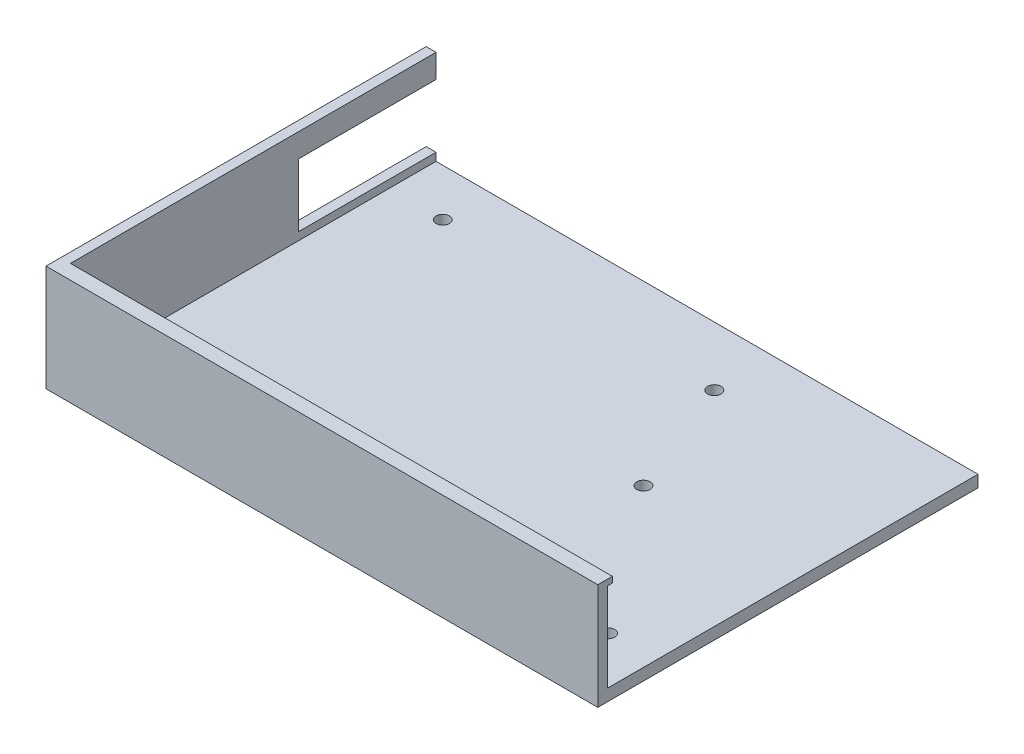
SolidWorks part; units mm, degrees
ref_plane "Front Plane" through (0, 0, 0) normal (0, 0, 1) x (1, 0, 0)
ref_plane "Top Plane" through (0, 0, 0) normal (0, 1, 0) x (1, 0, 0)
ref_plane "Right Plane" through (0, 0, 0) normal (1, 0, 0) x (0, 0, -1)
sketch "Sketch1" plane through (0, 0, 0) normal (0, 1, 0) x (1, 0, 0)
  line L1 (-140.2, -96.6) -> (140.2, -96.6)
  line L2 (-140.2, -96.6) -> (-140.2, 96.6)
  line L3 (-140.2, 96.6) -> (140.2, 96.6)
  line L4 (140.2, -96.6) -> (140.2, 96.6)
  line L5 (-140.2, -96.6) -> (140.2, 96.6) construction
  line L6 (-140.2, 96.6) -> (140.2, -96.6) construction
  point P0 (0, 0)
  dimension "D1" = 280.4
  dimension "D2" = 193.2
extrude "Shell Block" add sketch "Sketch1" along normal blind 27
ref_plane "Shell Front" through (0, 27, 0) normal (0, 1, 0) x (1, 0, 0)
sketch "Sketch2" plane through (0, 27, 0) normal (0, 1, 0) x (1, 0, 0)
  line L1 (-137.7, -92.9) -> (137.7, -92.9)
  line L2 (-137.7, -92.9) -> (-137.7, 92.9)
  line L3 (-137.7, 92.9) -> (137.7, 92.9)
  line L4 (137.7, -92.9) -> (137.7, 92.9)
  line L5 (-137.7, -92.9) -> (137.7, 92.9) construction
  line L6 (-137.7, 92.9) -> (137.7, -92.9) construction
  point P0 (0, 0)
  dimension "D1" = 275.4
  dimension "D2" = 185.8
extrude "Front Opening" cut sketch "Sketch2" against normal blind 1.5
ref_plane "Under Lip" through (0, 25.5, 0) normal (0, 1, 0) x (1, 0, 0)
sketch "Sketch3" plane through (0, 25.5, 0) normal (0, 1, 0) x (1, 0, 0)
  line L1 (-137.7, -94.1) -> (137.7, -94.1)
  line L2 (-137.7, -94.1) -> (-137.7, 94.1)
  line L3 (-137.7, 94.1) -> (137.7, 94.1)
  line L4 (137.7, -94.1) -> (137.7, 94.1)
  line L5 (-137.7, -94.1) -> (137.7, 94.1) construction
  line L6 (-137.7, 94.1) -> (137.7, -94.1) construction
  point P0 (0, 0)
  dimension "D1" = 275.4
  dimension "D2" = 188.2
extrude "Display Pocket" cut sketch "Sketch3" against normal blind 22.5
ref_plane "Back Inner" through (0, 3, 0) normal (0, 1, 0) x (1, 0, 0)
sketch "Sketch4" plane through (0, 3, 0) normal (0, 1, 0) x (1, 0, 0)
  line L1 (66, 28) -> (69, 28)
  line L2 (66, 28) -> (66, 84)
  line L3 (66, 84) -> (69, 84)
  line L4 (69, 28) -> (69, 84)
  line L6 (66, -84) -> (69, -84)
  line L7 (66, -84) -> (66, -28)
  line L8 (66, -28) -> (69, -28)
  line L9 (69, -84) -> (69, -28)
  line L11 (74, 28) -> (77, 28)
  line L12 (74, 28) -> (74, 84)
  line L13 (74, 84) -> (77, 84)
  line L14 (77, 28) -> (77, 84)
  line L16 (74, -84) -> (77, -84)
  line L17 (74, -84) -> (74, -28)
  line L18 (74, -28) -> (77, -28)
  line L19 (77, -84) -> (77, -28)
  line L21 (82, 28) -> (85, 28)
  line L22 (82, 28) -> (82, 84)
  line L23 (82, 84) -> (85, 84)
  line L24 (85, 28) -> (85, 84)
  line L26 (82, -84) -> (85, -84)
  line L27 (82, -84) -> (82, -28)
  line L28 (82, -28) -> (85, -28)
  line L29 (85, -84) -> (85, -28)
  line L31 (90, 28) -> (93, 28)
  line L32 (90, 28) -> (90, 84)
  line L33 (90, 84) -> (93, 84)
  line L34 (93, 28) -> (93, 84)
  line L36 (90, -84) -> (93, -84)
  line L37 (90, -84) -> (90, -28)
  line L38 (90, -28) -> (93, -28)
  line L39 (93, -84) -> (93, -28)
  line L41 (98, 28) -> (101, 28)
  line L42 (98, 28) -> (98, 84)
  line L43 (98, 84) -> (101, 84)
  line L44 (101, 28) -> (101, 84)
  line L46 (98, -84) -> (101, -84)
  line L47 (98, -84) -> (98, -28)
  line L48 (98, -28) -> (101, -28)
  line L49 (101, -84) -> (101, -28)
  line L51 (106, 28) -> (109, 28)
  line L52 (106, 28) -> (106, 84)
  line L53 (106, 84) -> (109, 84)
  line L54 (109, 28) -> (109, 84)
  line L56 (106, -84) -> (109, -84)
  line L57 (106, -84) -> (106, -28)
  line L58 (106, -28) -> (109, -28)
  line L59 (109, -84) -> (109, -28)
  line L61 (114, 28) -> (117, 28)
  line L62 (114, 28) -> (114, 84)
  line L63 (114, 84) -> (117, 84)
  line L64 (117, 28) -> (117, 84)
  line L66 (114, -84) -> (117, -84)
  line L67 (114, -84) -> (114, -28)
  line L68 (114, -28) -> (117, -28)
  line L69 (117, -84) -> (117, -28)
  line L71 (122, 28) -> (125, 28)
  line L72 (122, 28) -> (122, 84)
  line L73 (122, 84) -> (125, 84)
  line L74 (125, 28) -> (125, 84)
  line L76 (122, -84) -> (125, -84)
  line L77 (122, -84) -> (122, -28)
  line L78 (122, -28) -> (125, -28)
  line L79 (125, -84) -> (125, -28)
extrude "Vent Slots" cut sketch "Sketch4" against normal blind 4
sketch "Sketch5" plane through (0, 0, 0) normal (1, 0, 0) x (0, 0, -1)
  line L1 (-35, 5) -> (35, 5)
  line L2 (-35, 5) -> (-35, 21)
  line L3 (-35, 21) -> (35, 21)
  line L4 (35, 5) -> (35, 21)
extrude "Cable Exit (+X short side)" cut sketch "Sketch5" against normal blind 141.2
sketch "Sketch6" plane through (0, 3, 0) normal (0, 1, 0) x (1, 0, 0)
  circle A0 centre (-40, -45) radius 1.7
  circle A1 centre (-40, 45) radius 1.7
  circle A2 centre (40, -45) radius 1.7
  circle A3 centre (40, 45) radius 1.7
  circle A4 centre (-52, -15) radius 1.7
  circle A5 centre (-52, 15) radius 1.7
  circle A6 centre (52, -15) radius 1.7
  circle A7 centre (52, 15) radius 1.7
  circle A8 centre (-12, -82) radius 1.7
  circle A9 centre (-12, 82) radius 1.7
  circle A10 centre (12, -82) radius 1.7
  circle A11 centre (12, 82) radius 1.7
  circle A12 centre (-124, -12) radius 1.7
  circle A13 centre (-124, 12) radius 1.7
  circle A14 centre (124, -12) radius 1.7
  circle A15 centre (124, 12) radius 1.7
extrude "Bolt Holes" cut sketch "Sketch6" against normal blind 4
sketch "Sketch7" plane through (0, 0, 0) normal (0, 1, 0) x (1, 0, 0)
  line L1 (200, -200) -> (0, -200)
  line L2 (200, -200) -> (200, 200)
  line L3 (200, 200) -> (0, 200)
  line L4 (0, -200) -> (0, 200)
extrude "Keep one half (X)" cut sketch "Sketch7" against normal through all and the other way through all
sketch "Sketch8" plane through (0, 0, 0) normal (0, 1, 0) x (1, 0, 0)
  line L1 (-200, 0) -> (200, 0)
  line L2 (-200, 0) -> (-200, 200)
  line L3 (-200, 200) -> (200, 200)
  line L4 (200, 0) -> (200, 200)
extrude "Keep one quarter (Z)" cut sketch "Sketch8" against normal through all and the other way through all
equation "\"DispL\"= 274.2"
equation "\"DispW\"= 187.0"
equation "\"DispT\"= 20.0"
equation "\"Clr\"= 0.6"
equation "\"Wall\"= 2.5"
equation "\"BackT\"= 3.0"
equation "\"CableRoom\"= 4.0"
equation "\"LipW\"= 1.2"
equation "\"LipT\"= 1.5"
equation "\"CableW\"= 70.0"
equation "\"CableH\"= 16.0"
equation "\"BoltD\"= 3.4"
equation "\"ShellL\"= \"DispL\" + 2 * \"Clr\" + 2 * \"Wall\""
equation "\"ShellW\"= \"DispW\" + 2 * \"Clr\" + 2 * \"Wall\""
equation "\"ShellH\"= \"BackT\" + \"DispT\" + \"CableRoom\""
equation "\"D1@Sketch1\" = \"ShellL\""
equation "\"D2@Sketch1\" = \"ShellW\""
equation "\"D1@Shell Block\" = \"ShellH\""
equation "\"D1@Shell Front\" = \"ShellH\""
equation "\"D1@Sketch2\" = \"DispL\" + 2 * \"Clr\""
equation "\"D2@Sketch2\" = \"DispW\" + 2 * \"Clr\" - 2 * \"LipW\""
equation "\"D1@Front Opening\" = \"LipT\""
equation "\"D1@Under Lip\" = \"ShellH\" - \"LipT\""
equation "\"D1@Sketch3\" = \"DispL\" + 2 * \"Clr\""
equation "\"D2@Sketch3\" = \"DispW\" + 2 * \"Clr\""
equation "\"D1@Display Pocket\" = \"ShellH\" - \"LipT\" - \"BackT\""
equation "\"D1@Back Inner\" = \"BackT\""
